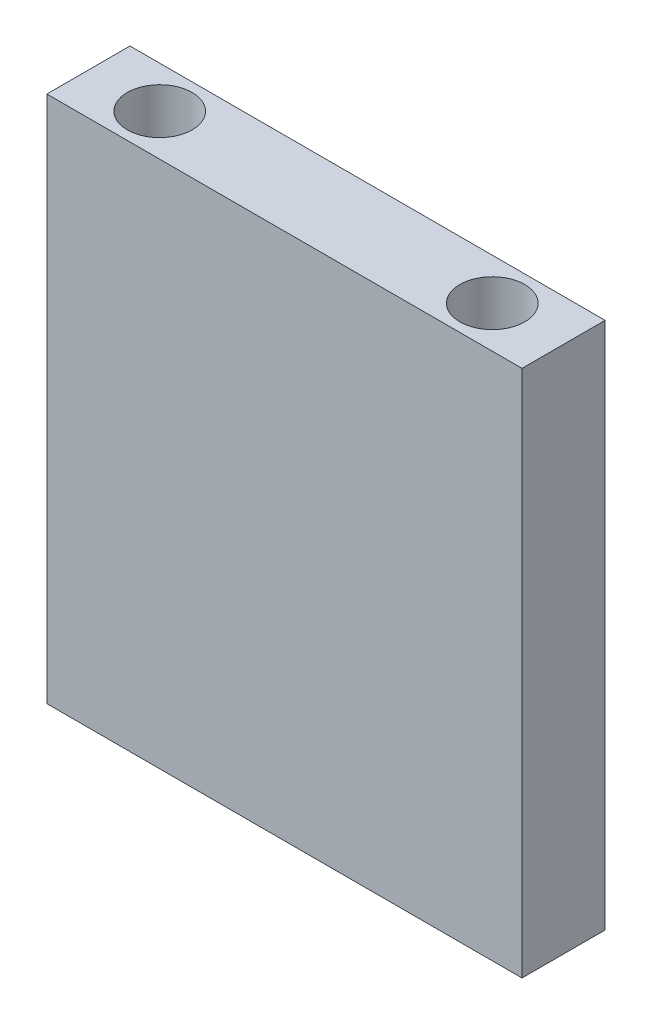
SolidWorks part; units mm, degrees
ref_plane "Front Plane" through (0, 0, 0) normal (0, 0, 1) x (1, 0, 0)
ref_plane "Top Plane" through (0, 0, 0) normal (0, 1, 0) x (1, 0, 0)
ref_plane "Right Plane" through (0, 0, 0) normal (1, 0, 0) x (0, 0, -1)
sketch "Sketch1" plane through (0, 0, 0) normal (0, 0, 1) x (1, 0, 0)
  line L1 (-14.2875, -15.875) -> (14.2875, -15.875)
  line L2 (-14.2875, -15.875) -> (-14.2875, 15.875)
  line L3 (-14.2875, 15.875) -> (14.2875, 15.875)
  line L4 (14.2875, -15.875) -> (14.2875, 15.875)
  line L5 (-14.2875, -15.875) -> (14.2875, 15.875) construction
  line L6 (-14.2875, 15.875) -> (14.2875, -15.875) construction
  point P0 (0, 0)
  dimension "D1" = 31.75
  dimension "D2" = 28.575
extrude "Boss-Extrude1" add sketch "Sketch1" along normal mid plane 5
sketch "Sketch3" plane through (0, 15.875, 0) normal (0, 1, 0) x (1, 0, 0)
  line L0 (-14.2875, 0) -> (14.2875, 0) construction
  line L1 (-14.2875, -2.5) -> (-14.2875, 2.5) construction
  line L2 (14.2875, -2.5) -> (14.2875, 2.5) construction
  line L3 (0, 2.5) -> (0, -2.5) construction
  line L4 (14.2875, 2.5) -> (-14.2875, 2.5) construction
  line L5 (14.2875, -2.5) -> (-14.2875, -2.5) construction
  circle A0 centre (-10, 0) radius 1.95
  circle A2 centre (10, 0) radius 1.95
  dimension "D2" = 3.9
  dimension "D1" = 10
extrude "Cut-Extrude1" cut sketch "Sketch3" against normal blind 5.2
